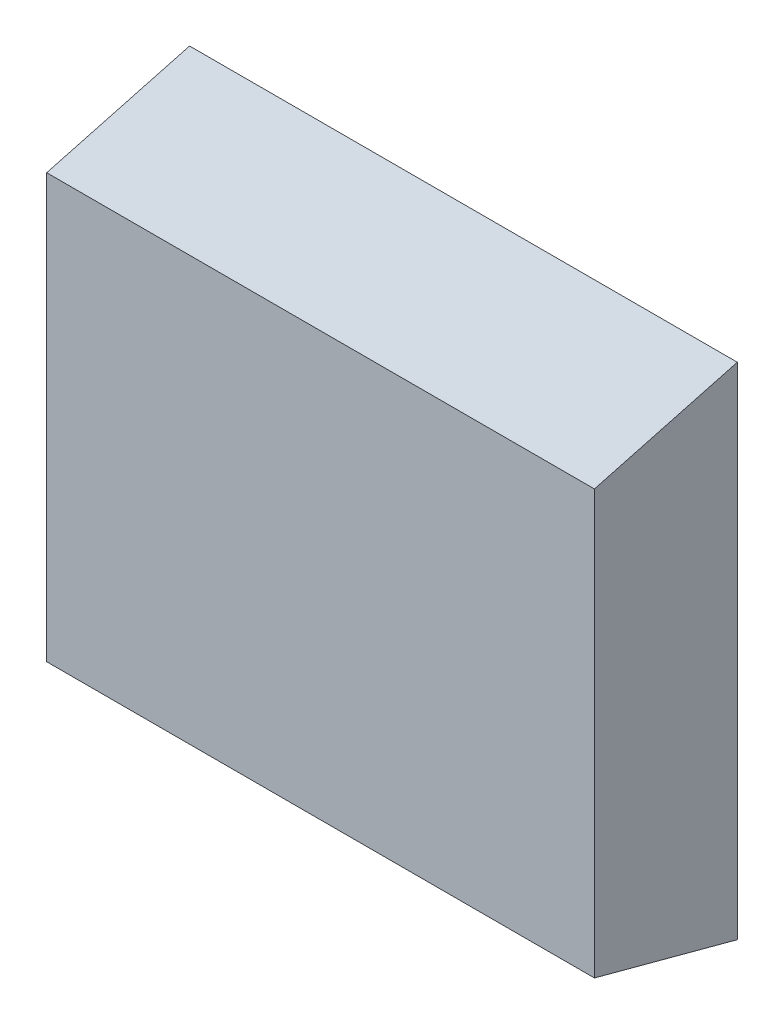
SolidWorks part; units mm, degrees
ref_plane "Front Plane" through (0, 0, 0) normal (0, 0, 1) x (1, 0, 0)
ref_plane "Top Plane" through (0, 0, 0) normal (0, 1, 0) x (1, 0, 0)
ref_plane "Right Plane" through (0, 0, 0) normal (1, 0, 0) x (0, 0, -1)
sketch "Esboço1" plane through (0, 0, 0) normal (0, 0, 1) x (1, 0, 0)
  line L1 (-17.25, -15.75) -> (17.25, -15.75)
  line L2 (-17.25, -15.75) -> (-17.25, 15.75)
  line L3 (-17.25, 15.75) -> (17.25, 15.75)
  line L4 (17.25, -15.75) -> (17.25, 15.75)
  line L5 (-17.25, -15.75) -> (17.25, 15.75) construction
  line L6 (-17.25, 15.75) -> (17.25, -15.75) construction
  point P0 (0, 0)
  dimension "D1" = 31.5
  dimension "D2" = 34.5
extrude "Ressalto-extrusão1" add sketch "Esboço1" along normal blind 9
chamfer "Chanfro1" distance 9 angle 15 2 edges at (0, -15.75, 9) (0, 15.75, 9) first distance on face at (0, -15.75, 4.5) first distance on face at (0, 15.75, 4.5)
